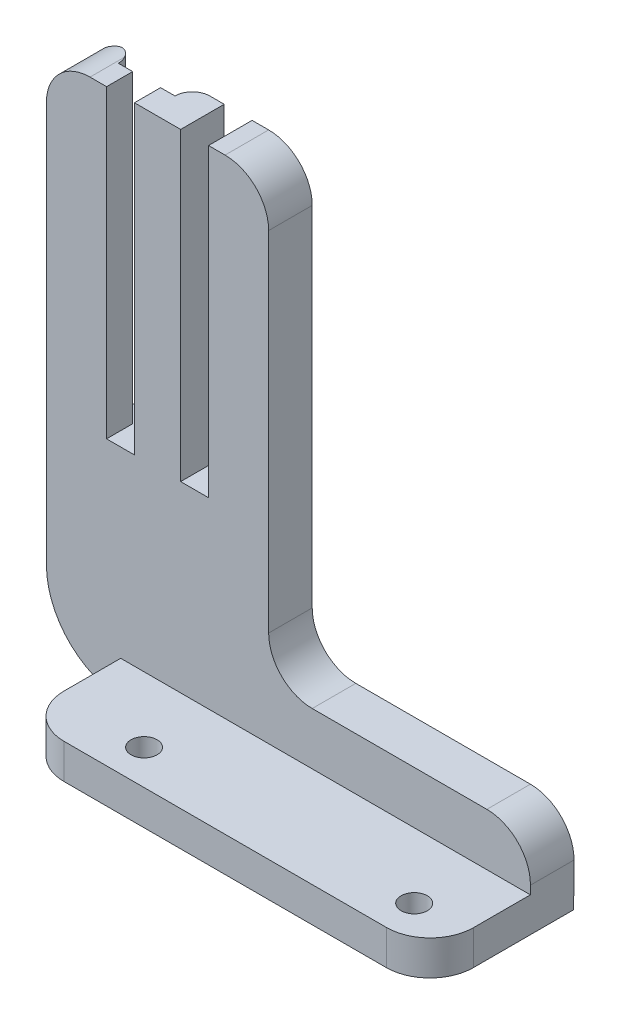
SolidWorks part; units mm, degrees
material "ABS generico"
ref_plane "Front Plane" through (0, 0, 0) normal (0, 0, 1) x (1, 0, 0)
ref_plane "Top Plane" through (0, 0, 0) normal (0, 1, 0) x (1, 0, 0)
ref_plane "Right Plane" through (0, 0, 0) normal (1, 0, 0) x (0, 0, -1)
sketch "Sketch1" plane through (0, 0, 0) normal (0, 0, 1) x (1, 0, 0)
  line L0 (24.5834, -25) -> (24.6606, -15)
  line L1 (24.5834, -25) -> (-30.9167, -25)
  line L2 (-5.4167, 0) -> (-5.4167, 35) construction
  line L3 (-5.4167, 35) -> (-12.3167, 35)
  line L4 (-30.9167, -25) -> (-30.9167, 35)
  line L5 (22.0833, -25) -> (-30.9167, 35) construction
  line L6 (24.6606, -15) -> (-5.4167, -15)
  line L7 (-13.9167, 0) -> (-13.9167, 35) construction
  line L9 (24.5834, -15) -> (-30.9167, -15) construction
  line L10 (-12.3167, 0) -> (-12.3167, 35)
  line L11 (-15.5167, 0) -> (-15.5167, 35)
  line L12 (-5.4167, -15) -> (-5.4167, 35)
  line L13 (-24.0167, 35) -> (-30.9167, 35)
  line L14 (-15.5167, 35) -> (-20.8167, 35)
  line L16 (-24.0167, 0) -> (-24.0167, 35)
  line L18 (-18, -10) -> (-18, 25) construction
  line L20 (-20.8167, 0) -> (-20.8167, 35)
  line L22 (-20.8167, 0) -> (-24.0167, 0)
  line L24 (-12.3167, 0) -> (-15.5167, 0)
  line L25 (-15.5167, -15) -> (-15.5167, 35) construction
  line L26 (-13.9167, -15) -> (-13.9167, 35) construction
  line L27 (-12.3167, -15) -> (-12.3167, 35) construction
  point P0 (0, 0)
  point P3 (26.5, 35)
  point P6 (-18, -25)
  point P10 (-16.4, -25)
  point P12 (-19.6, -25)
  point P18 (22.2762, 0)
  point P19 (-26.5, -10)
  dimension "D1" = 53
  dimension "D2" = 60
  dimension "D3" = 10
  dimension "D7" = 1.6
  dimension "D8" = 1.6
  dimension "D9" = 8.5
extrude "Extrude1" add sketch "Sketch1" along normal blind 5
sketch "Sketch3" plane through (0, 0, 5) normal (0, 0, 1) x (1, 0, 0)
  line L0 (22.0833, -10.5045) -> (22.0833, -32.7354) construction
  line L2 (-15.5167, 0) -> (-15.5167, -46) construction
  line L3 (-15.5167, -23) -> (22.0833, -23) construction
  line L4 (3.2833, -23) -> (3.2833, 0) construction
  line L5 (-15.5167, -25) -> (35.4785, -25) construction
  line L6 (-22.3949, -21) -> (24.6143, -21)
  line L8 (-22.3949, -25) -> (24.5834, -25)
  line L9 (-22.3949, -25) -> (-22.3949, -21)
  line L10 (-15.5167, -21) -> (22.0833, -25) construction
  line L11 (-15.5167, -25) -> (22.0833, -21) construction
  line L12 (24.6143, -21) -> (24.5834, -25)
  line L13 (24.5834, -25) -> (24.6606, -15) construction
  line L14 (-30.9167, -25) -> (24.5834, -25) construction
  dimension "D1" = 2
extrude "Extrude2" add sketch "Sketch3" along normal blind 11.5
sketch "Sketch4" plane through (0, 35, 0) normal (0, 1, 0) x (1, 0, 0)
  line L0 (-20.8167, 0) -> (-24.0167, 0) construction
  line L1 (-25.6667, -2) -> (-19.1667, -2)
  line L2 (-25.6667, -2) -> (-25.6667, 2)
  line L3 (-25.6667, 2) -> (-19.1667, 2)
  line L4 (-19.1667, -2) -> (-19.1667, 2)
  line L5 (-25.6667, -2) -> (-19.1667, 2) construction
  line L6 (-25.6667, 2) -> (-19.1667, -2) construction
  point P0 (-22.4167, 0)
  dimension "D1" = 6.5
  dimension "D2" = 4
sketch "Sketch5" plane through (0, -21, 0) normal (0, 1, 0) x (1, 0, 0)
  line L0 (17.6784, -12.4986) -> (-11.1079, -12.5014) construction
  line L1 (3.2852, -12.5) -> (3.2852, -16.5) construction
  line L2 (-15.5167, -16.5) -> (22.0833, -16.5) construction
  circle A0 centre (-12.2148, -12.5015) radius 1.5
  circle A1 centre (18.7852, -12.5015) radius 1.5
  dimension "D1" = 3
  dimension "D2" = 15.5
  dimension "D3" = 4
extrude "Extrude3" cut sketch "Sketch5" against normal up to surface (4 mm away) up to face at (-10.2862, -25, 8.125)
fillet "Fillet2" radius 5 2 edges at (-22.3949, -23, 16.5) (24.5988, -23, 16.5)
fillet "Fillet3" radius 5 4 edges at (-30.9167, 35, 2.5) (24.6606, -15, 2.5) (-5.4167, -15, 2.5) (-5.4167, 35, 2.5)
fillet "Fillet4" radius 9 1 edges at (-30.9167, -25, 2.5)
extrude "Extrude4" cut sketch "Sketch4" against normal up to surface (35 mm away) up to face at (-22.4167, 0, 2.5)
fillet "Fillet1" radius 2 2 edges at (-19.1667, 17.5, 0) (-25.6667, 17.5, 0)
